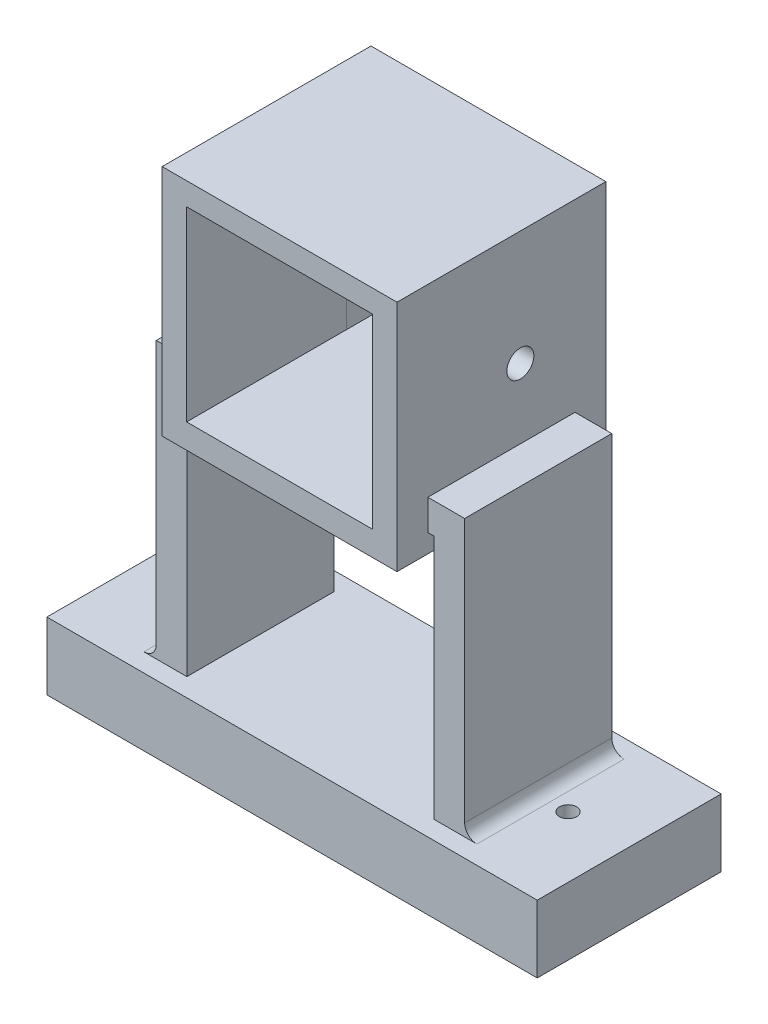
SolidWorks part; units mm, degrees
ref_plane "Front Plane" through (0, 0, 0) normal (0, 0, 1) x (1, 0, 0)
ref_plane "Top Plane" through (0, 0, 0) normal (0, 1, 0) x (1, 0, 0)
ref_plane "Right Plane" through (0, 0, 0) normal (1, 0, 0) x (0, 0, -1)
sketch "Sketch2" plane through (0, 0, 0) normal (0, 0, 1) x (1, 0, 0)
  line L0 (-5.08, -5.08) -> (43.58, -5.08)
  line L1 (0, 0) -> (38.5, 0) construction
  line L2 (0, 0) -> (0, 38.2) construction
  line L3 (0, 38.2) -> (38.5, 38.2) construction
  line L4 (38.5, 0) -> (38.5, 38.2) construction
  line L5 (43.58, -5.08) -> (43.58, 43.28)
  line L6 (-5.08, 43.28) -> (43.58, 43.28)
  line L7 (-5.08, -5.08) -> (-5.08, 43.28)
  dimension "D1" = 38.5
  dimension "D2" = 38.2
  dimension "D3" = 5.08
extrude "Boss-Extrude1" add sketch "Sketch2" along normal blind 43.2689
sketch "Sketch3" plane through (0, 0, 0) normal (0, 0, -1) x (-1, 0, 0)
  line L0 (-43.58, -5.08) -> (-43.58, 43.28) construction
  line L1 (0, 0) -> (-37.992, 0)
  line L2 (0, 0) -> (0, 8.128)
  line L3 (0, 8.128) -> (-37.992, 8.128)
  line L4 (-37.992, 0) -> (-37.992, 8.128)
  dimension "D1" = 5.588
  dimension "D2" = 8.128
extrude "Cut-Extrude1" cut sketch "Sketch3" against normal blind 38.1889
sketch "Sketch4" plane through (0, 0, 43.2689) normal (0, 0, 1) x (1, 0, 0)
  line L0 (43.58, -5.08) -> (43.58, 43.28) construction
  line L1 (-0.0064, 38.608) -> (38.5, 38.608)
  line L2 (-0.0064, 38.608) -> (-0.0064, 0)
  line L3 (-0.0064, 0) -> (38.5, 0)
  line L4 (38.5, 38.608) -> (38.5, 0)
  line L5 (-5.08, -5.08) -> (43.58, -5.08) construction
  dimension "D1" = 38.5064
  dimension "D2" = 38.608
  dimension "D3" = 5.08
  dimension "D4" = 5.08
extrude "Cut-Extrude2" cut sketch "Sketch4" against normal blind 33.1089
sketch "Sketch6" plane through (38.5, 0, 0) normal (-1, 0, 0) x (0, 0, 1)
  circle A0 centre (17.7143, 19.508) radius 2.794
  dimension "D1" = 5.588
extrude "Cut-Extrude3" cut sketch "Sketch6" against normal blind 23.622 and the other way blind 78.486
sketch "Sketch7" plane through (43.58, 0, 0) normal (1, 0, 0) x (0, 0, -1)
  line L0 (-21.6345, -5.08) -> (-21.6345, 14.9944) construction
  line L1 (-43.2689, -5.08) -> (0, -5.08) construction
  line L3 (-36.8745, 5.08) -> (-6.3945, 5.08)
  line L4 (-36.8745, 5.08) -> (-36.8744, -1.27)
  line L5 (-36.8744, -1.27) -> (-6.3945, -1.27)
  line L6 (-6.3945, 5.08) -> (-6.3945, -1.27)
  line L7 (-36.8745, 5.08) -> (-6.3945, -1.27) construction
  line L8 (-36.8744, -1.27) -> (-6.3945, 5.08) construction
  point P4 (-21.6345, 1.905)
  point P9 (-21.6345, 3.2938)
  dimension "D1" = 3.81
  dimension "D2" = 6.35
  dimension "D3" = 30.48
extrude "Boss-Extrude2" add sketch "Sketch7" along normal blind 7.62
sketch "Sketch9" plane through (0, 0, 36.8744) normal (0, 0, 1) x (1, 0, 0)
  line L1 (51.2, -1.27) -> (44.85, -1.27)
  line L2 (51.2, -1.27) -> (51.2, -52.07)
  line L3 (51.2, -52.07) -> (44.85, -52.07)
  line L4 (44.85, -1.27) -> (44.85, -52.07)
  dimension "D1" = 6.35
  dimension "D2" = 50.8
extrude "Boss-Extrude3" add sketch "Sketch9" against normal blind 30.48
ref_plane "Plane1" through (19.25, 0, 0) normal (1, 0, 0) x (0, 0, -1)
mirror "Mirror1" about plane through (19.25, 0, 0) normal (1, 0, 0) of "Boss-Extrude3", "Boss-Extrude2"
sketch "Sketch11" plane through (0, -52.07, 0) normal (0, -1, 0) x (1, 0, 0)
  line L0 (-12.7, 21.6345) -> (51.2, 21.6345) construction
  line L1 (-31.55, 40.6844) -> (70.05, 40.6844)
  line L2 (-31.55, 40.6844) -> (-31.55, 2.5844)
  line L3 (-31.55, 2.5844) -> (70.05, 2.5844)
  line L4 (70.05, 40.6844) -> (70.05, 2.5844)
  line L5 (-12.7, 6.3944) -> (-12.7, 36.8744) construction
  line L6 (51.2, 6.3944) -> (51.2, 36.8744) construction
  line L8 (19.25, -23.7979) -> (19.25, 23.7979) construction
  dimension "D1" = 38.1
  dimension "D2" = 19.05
  dimension "D3" = 101.6
  dimension "D4" = 50.8
extrude "Boss-Extrude4" add sketch "Sketch11" along normal blind 13.97
sketch "Sketch14" plane through (0, -66.04, 0) normal (0, -1, 0) x (1, 0, 0)
  line L0 (-31.55, 21.6345) -> (88.8469, 21.6345) construction
  line L1 (-31.55, 40.6844) -> (-31.55, 2.5844) construction
  line L2 (19.25, 2.7133) -> (19.25, 53.7181) construction
  line L3 (19.25, -23.7979) -> (19.25, 23.7979) construction
  circle A0 centre (19.25, 21.6345) radius 38.127 construction
  circle A1 centre (57.377, 21.6344) radius 1.778
  circle A2 centre (-18.877, 21.6344) radius 1.778
  dimension "D1" = 76.254
  dimension "D2" = 3.556
extrude "Cut-Extrude4" cut sketch "Sketch14" against normal up to vertex (64.77 mm away) up to point (43.58, -1.27, 6.3945)
fillet "Fillet1" radius 2.54 2 edges at (-12.7, -52.07, 21.6345) (51.2, -52.07, 21.6345)
